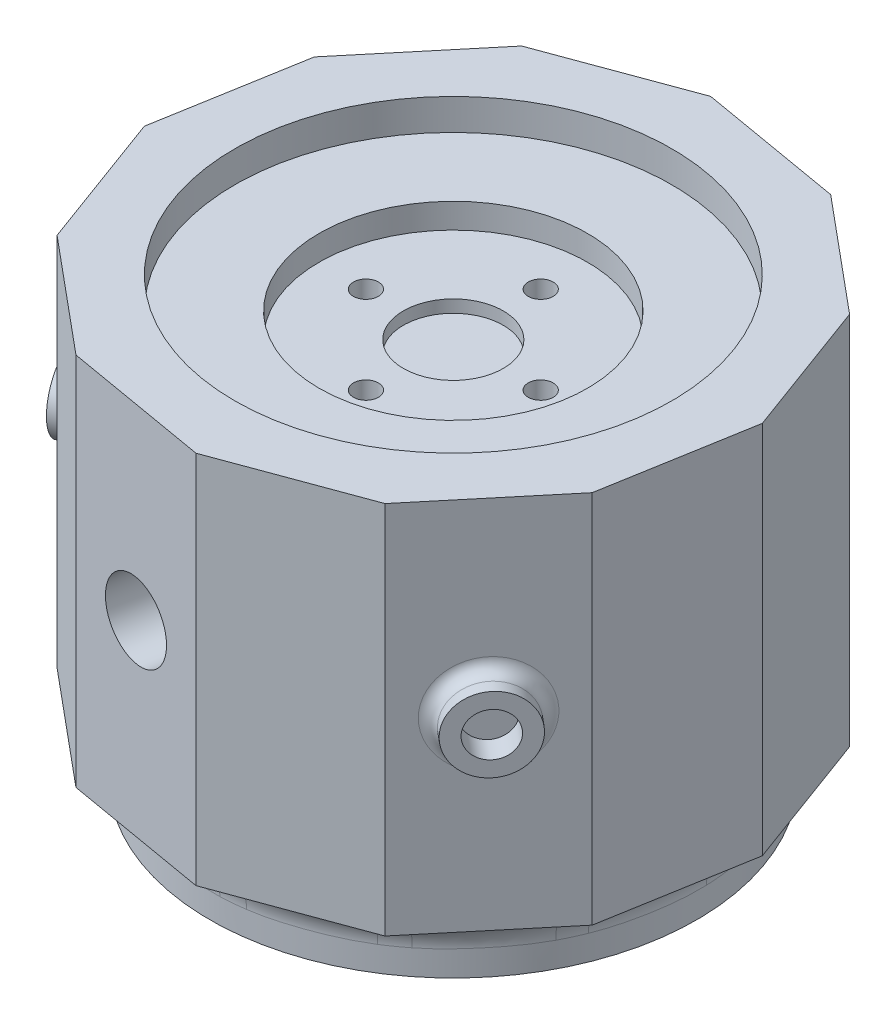
SolidWorks part; units mm, degrees
ref_plane "Front Plane" through (0, 0, 0) normal (0, 0, 1) x (1, 0, 0)
ref_plane "Top Plane" through (0, 0, 0) normal (0, 1, 0) x (1, 0, 0)
ref_plane "Right Plane" through (0, 0, 0) normal (1, 0, 0) x (0, 0, -1)
sketch "Sketch1" plane through (0, 0, 0) normal (0, 1, 0) x (1, 0, 0)
  line L0 (-18.6086, -13.1327) -> (-9.5492, -20.6776)
  line L1 (18.6086, 13.1327) -> (9.5492, 20.6776)
  line L2 (9.5492, 20.6776) -> (-2.0689, 22.6819)
  line L3 (-2.0689, 22.6819) -> (-13.1327, 18.6086)
  line L4 (-13.1327, 18.6086) -> (-20.6776, 9.5492)
  line L5 (-20.6776, 9.5492) -> (-22.6819, -2.0689)
  line L6 (-22.6819, -2.0689) -> (-18.6086, -13.1327)
  line L7 (-9.5492, -20.6776) -> (2.0689, -22.6819)
  line L8 (2.0689, -22.6819) -> (13.1327, -18.6086)
  line L9 (13.1327, -18.6086) -> (20.6776, -9.5492)
  line L10 (20.6776, -9.5492) -> (22.6819, 2.0689)
  line L11 (22.6819, 2.0689) -> (18.6086, 13.1327)
  circle A0 centre (0, 0) radius 22 construction
  circle A1 centre (0, 0) radius 17.5
  point P16 (0, 0)
  dimension "D1" = 35
  dimension "D2" = 44
extrude "Boss-Extrude1" add sketch "Sketch1" along normal blind 30
sketch "Sketch2" plane through (0, 30, 0) normal (0, 1, 0) x (1, 0, 0)
  circle A0 centre (0, 0) radius 17.5
extrude "Boss-Extrude2" add sketch "Sketch2" against normal blind 4.5 from offset 2.5 offset against normal yes
sketch "Sketch3" plane through (0, 23, 0) normal (0, -1, 0) x (1, 0, 0)
  circle A0 centre (0, 0) radius 15.5
  circle A1 centre (0, 0) radius 17.5
  dimension "D1" = 31
  dimension "D2" = 35
extrude "Cut-Extrude1" cut sketch "Sketch3" against normal blind 1.8
sketch "Sketch4" plane through (0, 0, 0) normal (0, -1, 0) x (1, 0, 0)
  circle A0 centre (0, 0) radius 17.5
  circle A1 centre (0, 0) radius 19.5
  dimension "D1" = 35
  dimension "D2" = 39
extrude "Boss-Extrude3" add sketch "Sketch4" along normal blind 5
fillet "Fillet1" radius 3 1 edges at (0, 0, 19.5)
sketch "Sketch5" plane through (3.7401, 0, -21.6797) normal (0.17, 0, -0.9854) x (-0.9854, 0, -0.17)
  line L0 (0, 30) -> (0, 0) construction
  line L1 (-5.8949, 30) -> (5.8949, 30) construction
  circle A0 centre (0, 15) radius 1.75
  circle A1 centre (0, 15) radius 3
  dimension "D2" = 3.5
  dimension "D3" = 6
  dimension "D1" = 15
extrude "Boss-Extrude4" add sketch "Sketch5" along normal blind 2
pattern_circular "CirPattern2" count 3 every 120 about axis through (0, -5, 0) along (0, -1, 0) of "Boss-Extrude4"
fillet "Fillet2" radius 1 3 edges at (6.6965, 15, -21.1697) (-21.6818, 15, 4.7856) (14.9853, 15, 16.3842)
sketch "Sketch6" plane through (0, 27.5, 0) normal (0, 1, 0) x (1, 0, 0)
  line L0 (0, 0) -> (17.5, 0) construction
  circle A0 centre (0, 0) radius 4
  circle A1 centre (0, 0) radius 17.5 construction
  circle A2 centre (7, 0) radius 1
  circle A3 centre (0, 0) radius 10.75
  circle A4 centre (0, -7) radius 1
  circle A5 centre (-7, 0) radius 1
  circle A6 centre (0, 7) radius 1
  point P19 (0, 0)
  dimension "D1" = 8
  dimension "D3" = 2
  dimension "D4" = 21.5
  dimension "D2" = 7
  dimension "D5" = 4
extrude "Cut-Extrude5" cut sketch "Sketch6" against normal blind 2 contours A0 A2 A3 A6 A5 A4 | A0 region at (0, 27.5, 0) region at (-10.4459, 27.5, 0)
extrude "Cut-Extrude6" cut sketch "Sketch6<3>" against normal blind 1 from surface contours A0 region at (0, 27.5, 0) starting at face at (7, 25.5, 1)
sketch "Sketch6<3>" plane through (0, 27.5, 0) normal (0, 1, 0) x (1, 0, 0) same geometry as "Sketch6"
extrude "Cut-Extrude7" cut sketch "Sketch6<4>" against normal through all both and the other way through all contours A5 | A6 | A4 | L0 A2 | A2 L0 region at (7, 27.5, 0.4244) region at (7, 27.5, -0.4244) region at (0, 27.5, 7) region at (-7, 27.5, 0) region at (0, 27.5, -7)
sketch "Sketch6<4>" plane through (0, 27.5, 0) normal (0, 1, 0) x (1, 0, 0) same geometry as "Sketch6"
sketch "Sketch7" plane through (-3.7401, 0, 21.6797) normal (-0.17, 0, 0.9854) x (0.9854, 0, 0.17)
  line L0 (0, 0) -> (0, 30) construction
  line L1 (-5.8949, 30) -> (5.8949, 30) construction
  line L2 (-4.717, 0) -> (4.717, 0) construction
  circle A0 centre (0, 15) radius 3
  dimension "D2" = 6
  dimension "D1" = 15
extrude "Cut-Extrude8" cut sketch "Sketch7" against normal blind 10
